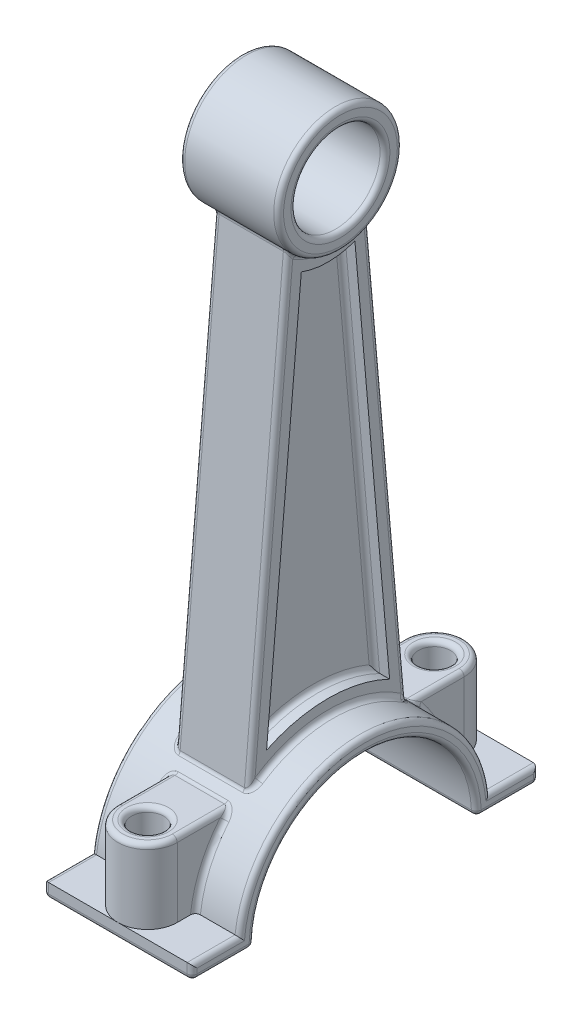
SolidWorks part; units mm, degrees
material "1023 Carbon Steel Sheet (SS)"
ref_plane "Front Plane" through (0, 0, 0) normal (0, 0, 1) x (1, 0, 0)
ref_plane "Top Plane" through (0, 0, 0) normal (0, 1, 0) x (1, 0, 0)
ref_plane "Right Plane" through (0, 0, 0) normal (1, 0, 0) x (0, 0, -1)
sketch "Sketch1" plane through (0, 0, 0) normal (1, 0, 0) x (0, 0, -1)
  line L0 (0, 0) -> (0, -120.4) construction
  line L1 (22.5, -120.4) -> (35, -120.4)
  line L2 (-22.5, -120.4) -> (-35, -120.4)
  line L3 (25.3229, -117.4) -> (35, -117.4)
  line L4 (-25.3229, -117.4) -> (-35, -117.4)
  line L5 (-35, -117.4) -> (-35, -120.4)
  line L6 (35, -117.4) -> (35, -120.4)
  line L7 (-8, -9.6047) -> (-15.9529, -100.5064)
  line L8 (8, -9.6047) -> (15.9529, -100.5064)
  circle A0 centre (0, 0) radius 12.5
  circle A1 centre (0, 0) radius 9
  arc A2 (22.5, -120.4) -> (-22.5, -120.4) centre (0, -120.4) ccw
  arc A3 (25.3229, -117.4) -> (-25.3229, -117.4) centre (0, -120.4) ccw
  dimension "D1" = 25
  dimension "D2" = 18
  dimension "D3" = 45
  dimension "D4" = 120.4
  dimension "D5" = 35
  dimension "D7" = 8
  dimension "D8" = 5
  dimension "D6" = 3
extrude "Boss-Extrude1" add sketch "Sketch1" along normal mid plane 20 contours A1 A0 region at (0, -12.1464, 0)
extrude "Boss-Extrude2" add sketch "Sketch1<3>" along normal mid plane 30 separate body contours L0 A3 L4 L5 L2 A2 | A3 L0 A2 L1 L6 L3 region at (0, -96.7509, -8.3111) region at (0, -96.4, 0.433)
sketch "Sketch1<3>" plane through (0, 0, 0) normal (1, 0, 0) x (0, 0, -1) same geometry as "Sketch1"
extrude "Boss-Extrude3" add sketch "Sketch1<4>" along normal mid plane 15 contours A0 L0 A3 L8 | L0 A0 L7 A3 region at (0, -58.5545, -6.2653) region at (0, -58.5545, 6.2653)
sketch "Sketch1<4>" plane through (0, 0, 0) normal (1, 0, 0) x (0, 0, -1) same geometry as "Sketch1"
sketch "Sketch2" plane through (0, -117.4, 0) normal (0, 1, 0) x (1, 0, 0)
  line L0 (0, 35) -> (0, 17) construction
  line L1 (15, 35) -> (-15, 35) construction
  line L4 (-6, 29) -> (-6, 17)
  line L5 (-6, 17) -> (6, 17)
  line L6 (6, 29) -> (6, 17)
  arc A0 (6, 29) -> (-6, 29) centre (0, 29) ccw
  dimension "D1" = 6
  dimension "D2" = 12
extrude "Boss-Extrude4" add sketch "Sketch2" along normal blind 15
sketch "Sketch3" plane through (0, -102.4, 0) normal (0, 1, 0) x (1, 0, 0)
  circle A0 centre (0, 29) radius 3.25
  dimension "D1" = 6.5
extrude "Cut-Extrude1" cut sketch "Sketch3" against normal through all
mirror "Mirror1" about plane through (0, 0, 0) normal (0, 0, 1) of "Cut-Extrude1", "Boss-Extrude4"
sketch "Sketch4" plane through (15, 0, 0) normal (1, 0, 0) x (0, 0, -1)
  line L0 (-22.5, -120.4) -> (22.5, -120.4)
  arc A0 (22.5, -120.4) -> (-22.5, -120.4) centre (0, -120.4) ccw construction
  arc A1 (22.5, -120.4) -> (-22.5, -120.4) centre (0, -120.4) ccw
extrude "Cut-Extrude2" cut sketch "Sketch4" against normal through all
sketch "Sketch5" plane through (7.5, 0, 0) normal (1, 0, 0) x (0, 0, -1)
  line L0 (12.4385, -94.7576) -> (5.4187, -14.522)
  line L1 (-5.4187, -14.522) -> (-12.4385, -94.7576)
  line L2 (-8, -9.6047) -> (-15.9529, -100.5064)
  line L3 (15.9529, -100.5064) -> (8, -9.6047)
  line L4 (-8, -9.6047) -> (-15.9529, -100.5064)
  line L5 (15.9529, -100.5064) -> (8, -9.6047)
  arc A0 (-5.4187, -14.522) -> (5.4187, -14.522) centre (0, 0) ccw
  arc A1 (12.4385, -94.7576) -> (-12.4385, -94.7576) centre (0, -120.4) ccw
  arc A2 (-8, -9.6047) -> (8, -9.6047) centre (0, 0) ccw
  arc A3 (15.9529, -100.5064) -> (-15.9529, -100.5064) centre (0, -120.4) ccw
  arc A4 (-8, -9.6047) -> (8, -9.6047) centre (0, 0) ccw
  arc A5 (15.9529, -100.5064) -> (-15.9529, -100.5064) centre (0, -120.4) ccw
  dimension "D2" = 3
  dimension "D1" = 0
extrude "Cut-Extrude3" cut sketch "Sketch5" against normal blind 3 contours A1 L0 A0 L1 region at (7.5, -58.957, 0)
mirror "Mirror2" about plane through (0, 0, 0) normal (1, 0, 0) of "Cut-Extrude3"
fillet "Fillet1" radius 1 60 edges at (7.5, -94.9, 0) (-7.5, -94.9, 0) (-6, -109.2901, -22.9526) (6, -109.2901, -22.9526) (6, -109.2901, 22.9526) (-6, -109.2901, 22.9526) (7.5, -55.0555, 11.9764) (0, -100.5064, 15.9529) (-7.5, -55.0555, 11.9764) (0, -100.5064, -15.9529) (7.5, -55.0555, -11.9764) (-7.5, -55.0555, -11.9764) (-6, -102.4, -23.5312) (0, -102.4, -35) (6, -102.4, -23.5312) (0, -102.4, -18.0624) (0, -102.4, -25.75) (0, -120.4, -22.5) (0, -120.4, -35) (0, -120.4, -25.75) (0, -120.4, 35) (0, -120.4, 22.5) (0, -120.4, 25.75) (6, -102.4, 23.5312) (0, -102.4, 35) (-6, -102.4, 23.5312) (0, -102.4, 18.0624) (0, -102.4, 25.75) (-15, -120.4, -28.75) (-15, -118.9, -35) (-15, -117.4, -30.1615) (-15, -94.9, 0) (-15, -117.4, 30.1615) (-15, -118.9, 35) (-15, -120.4, 28.75) (-15, -97.9, 0) (15, -120.4, 28.75) (15, -118.9, 35) (15, -117.4, 30.1615) (15, -94.9, 0) (15, -117.4, -30.1615) (15, -118.9, -35) (15, -120.4, -28.75) (15, -97.9, 0) (-4.5, -54.6398, -8.9286) (-4.5, -15.5, 0) (-4.5, -54.6398, 8.9286) (-4.5, -91.9, 0) (4.5, -54.6398, 8.9286) (4.5, -15.5, 0) (4.5, -54.6398, -8.9286) (4.5, -91.9, 0) (-10, 0, -9) (10, 0, -9) (-10, 0, -12.5) (10, 0, -12.5) (-7.5, -12.5, 0) (0, -9.6047, -8) (7.5, -12.5, 0) (0, -9.6047, 8)
